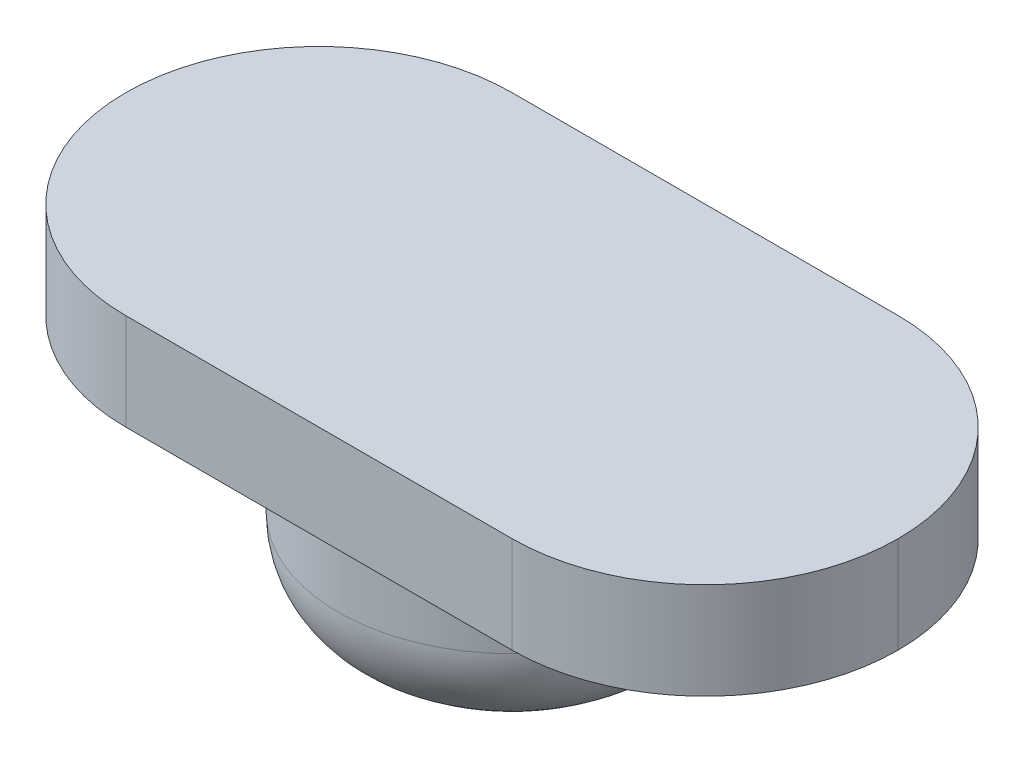
SolidWorks part; units mm, degrees
ref_plane "Front Plane" through (0, 0, 0) normal (0, 0, 1) x (1, 0, 0)
ref_plane "Top Plane" through (0, 0, 0) normal (0, 1, 0) x (1, 0, 0)
ref_plane "Right Plane" through (0, 0, 0) normal (1, 0, 0) x (0, 0, -1)
sketch "Sketch2" plane through (0, 0, 0) normal (0, -1, 0) x (1, 0, 0)
  line L0 (-40, -50) -> (40, -50) construction
  line L1 (-10, -35) -> (10, -35)
  line L2 (-10, -35) -> (-10, -45)
  line L3 (-10, -45) -> (10, -45)
  line L4 (10, -35) -> (10, -45)
  line L5 (50, -40) -> (50, -9) construction
  dimension "D1" = 5
  dimension "D2" = 10
  dimension "D3" = 20
  dimension "D4" = 40
extrude "Boss-Extrude1" add sketch "Sketch2" along normal blind 2.5
fillet "Fillet1" radius 5 4 edges at (-10, -1.25, -35) (-10, -1.25, -45) (10, -1.25, -45) (10, -1.25, -35)
sketch "Sketch3" plane through (0, -2.5, 0) normal (0, -1, 0) x (1, 0, 0)
  line L0 (5, -35) -> (-5, -35) construction
  circle A0 centre (0, -40) radius 4.5
  dimension "D2" = 9
  dimension "D1" = 5
extrude "Boss-Extrude2" add sketch "Sketch3" along normal blind 4.4
fillet "Fillet2" radius 2.5 1 edges at (0, -6.9, -44.5)
